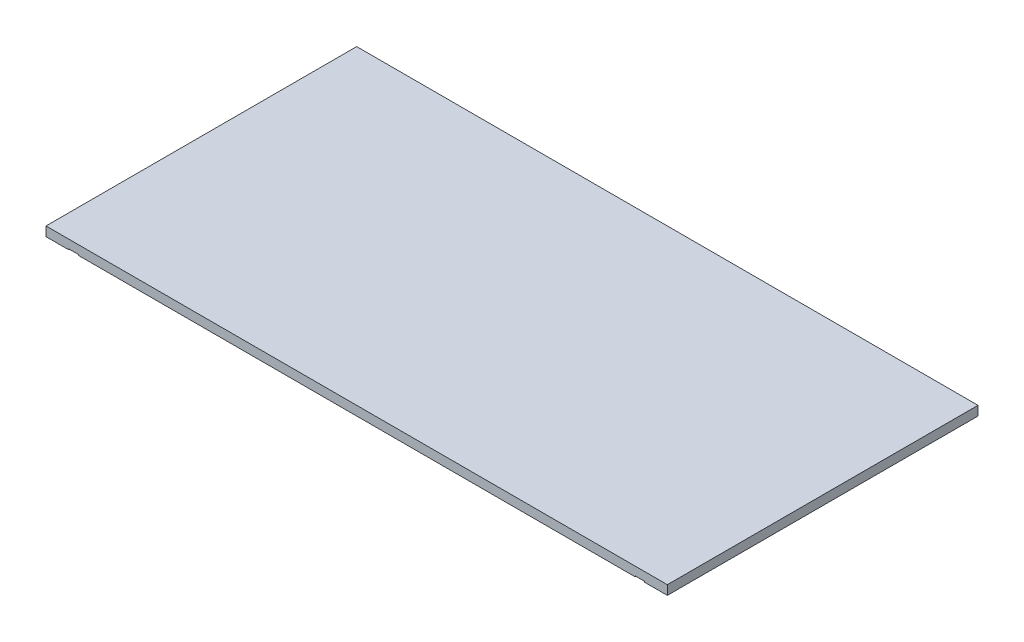
SolidWorks part; units mm, degrees
material "Cedar"
ref_plane "Front Plane" through (0, 0, 0) normal (0, 0, 1) x (1, 0, 0)
ref_plane "Top Plane" through (0, 0, 0) normal (0, 1, 0) x (1, 0, 0)
ref_plane "Right Plane" through (0, 0, 0) normal (1, 0, 0) x (0, 0, -1)
sketch "Sketch1" plane through (0, 0, 0) normal (0, 1, 0) x (1, 0, 0)
  line L1 (-609.6, -304.8) -> (609.6, -304.8)
  line L2 (-609.6, -304.8) -> (-609.6, 304.8)
  line L3 (-609.6, 304.8) -> (609.6, 304.8)
  line L4 (609.6, -304.8) -> (609.6, 304.8)
  line L5 (-609.6, -304.8) -> (609.6, 304.8) construction
  line L6 (-609.6, 304.8) -> (609.6, -304.8) construction
  point P0 (0, 0)
  dimension "D1" = 1219.2
  dimension "D2" = 609.6
extrude "Boss-Extrude1" add sketch "Sketch1" along normal blind 18.2562
sketch "Sketch2" plane through (0, 0, 0) normal (0, 1, 0) x (1, 0, 0)
  line L0 (609.6, 304.8) -> (-609.6, 304.8) construction
  line L1 (-565.15, 304.8) -> (-546.1, 304.8)
  line L2 (-565.15, 304.8) -> (-565.15, -304.8)
  line L3 (-565.15, -304.8) -> (-546.1, -304.8)
  line L4 (-546.1, 304.8) -> (-546.1, 9.525)
  line L5 (-609.6, -304.8) -> (609.6, -304.8) construction
  line L7 (-546.1, 9.525) -> (101.6, 9.525)
  line L8 (-546.1, 9.525) -> (-546.1, -9.525) construction
  line L9 (-546.1, -9.525) -> (-120.65, -9.525)
  line L12 (565.15, 304.8) -> (546.1, 304.8)
  line L13 (565.15, 304.8) -> (565.15, -304.8)
  line L14 (565.15, -304.8) -> (546.1, -304.8)
  line L15 (546.1, 304.8) -> (546.1, 9.525)
  line L17 (-120.65, -9.525) -> (-101.6, -9.525)
  line L18 (-120.65, -9.525) -> (-120.65, -304.8) construction
  line L19 (-120.65, -304.8) -> (-101.6, -304.8) construction
  line L20 (-101.6, -9.525) -> (-101.6, -304.8) construction
  line L21 (-546.1, -9.525) -> (-546.1, -304.8)
  line L23 (101.6, -9.525) -> (101.6, -304.8) construction
  line L24 (101.6, -304.8) -> (120.65, -304.8) construction
  line L25 (120.65, -9.525) -> (120.65, -304.8) construction
  line L26 (-101.6, -9.525) -> (101.6, -9.525)
  line L27 (0, 0) -> (0, -9.525) construction
  line L28 (546.1, -9.525) -> (546.1, -304.8)
  line L29 (120.65, -9.525) -> (546.1, -9.525)
  line L30 (-565.15, 304.8) -> (-609.6, 304.8) construction
  line L31 (565.15, 304.8) -> (609.6, 304.8) construction
  line L32 (-609.6, 304.8) -> (-609.6, -304.8) construction
  line L33 (120.65, 9.525) -> (546.1, 9.525)
  line L35 (101.6, 9.525) -> (101.6, 304.8)
  line L36 (101.6, 304.8) -> (120.65, 304.8)
  line L37 (120.65, 9.525) -> (120.65, 304.8)
  line L38 (-546.1, 0) -> (-609.6, 0) construction
  line L39 (101.6, -9.525) -> (120.65, -9.525)
  dimension "D1" = 19.05
  dimension "D3" = 425.45
  dimension "D4" = 203.2
  dimension "D5" = 44.45
extrude "Cut-Extrude1" cut sketch "Sketch2" along normal blind 1.5875
sketch "Sketch5" plane through (0, 1.5875, 0) normal (0, -1, 0) x (-1, 0, 0)
  line L0 (-546.1, -9.525) -> (546.1, -9.525) construction
  point P0 (0, -9.525)
sketch "Sketch6" plane through (0, 18.2562, 0) normal (0, 1, 0) x (1, 0, 0)
  line L0 (-609.6, -304.8) -> (609.6, -304.8) construction
  line L2 (-609.6, 304.8) -> (-609.6, -304.8)
  line L3 (-609.6, -304.8) -> (-590.55, -304.8)
  line L4 (-590.55, 285.75) -> (-590.55, -304.8)
  line L5 (546.1, -304.8) -> (565.15, -304.8) construction
  line L8 (-590.55, 285.75) -> (590.55, 285.75)
  line L11 (609.6, 304.8) -> (609.6, -304.8)
  line L12 (609.6, -304.8) -> (590.55, -304.8)
  line L13 (590.55, 285.75) -> (590.55, -304.8)
  line L14 (609.6, 304.8) -> (-609.6, 304.8) construction
  line L15 (609.6, 304.8) -> (-609.6, 304.8)
  line L16 (-590.55, 285.75) -> (-590.55, 304.8) construction
  line L17 (0, 0) -> (0, 285.75)
  line L18 (0, 0) -> (0, -304.8)
